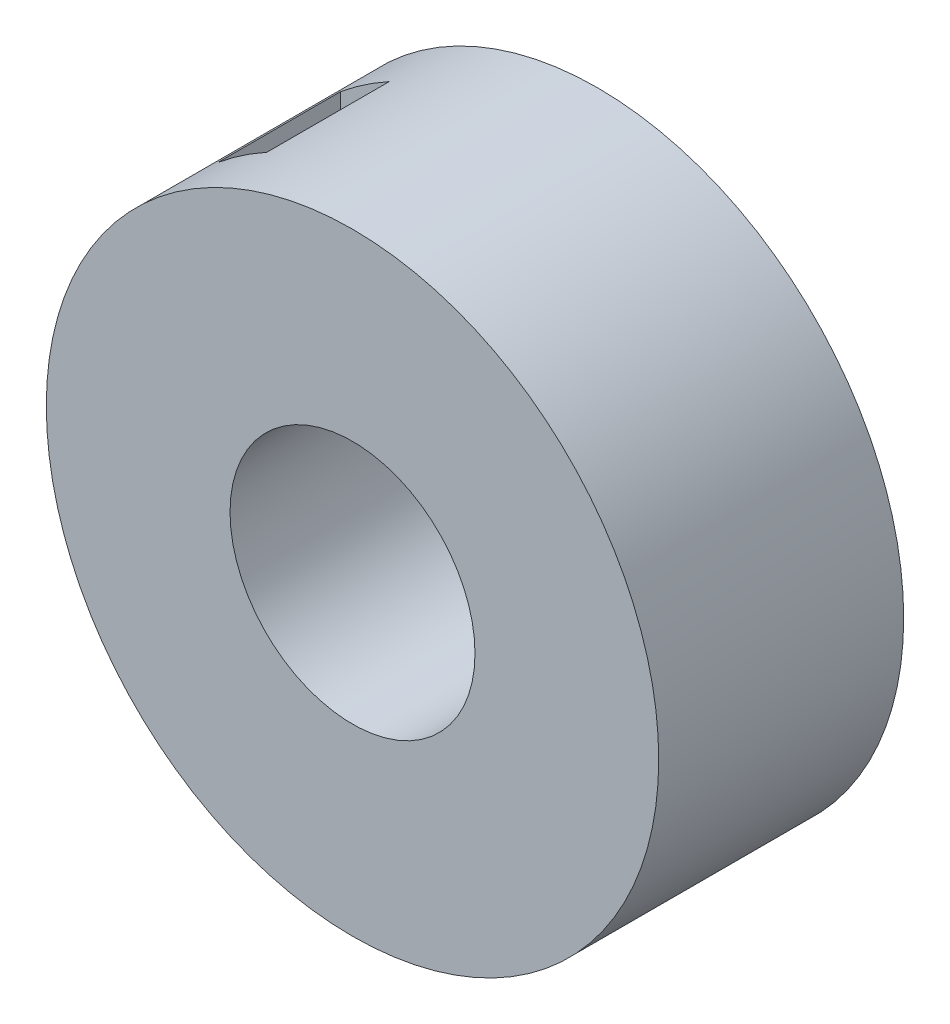
SolidWorks part; units mm, degrees
ref_plane "Alzado" through (0, 0, 0) normal (0, 0, 1) x (1, 0, 0)
ref_plane "Planta" through (0, 0, 0) normal (0, 1, 0) x (1, 0, 0)
ref_plane "Vista lateral" through (0, 0, 0) normal (1, 0, 0) x (0, 0, -1)
sketch "Croquis1" plane through (0, 0, 0) normal (0, 0, 1) x (1, 0, 0)
  circle A0 centre (0, 0) radius 0.625
  circle A1 centre (0, 0) radius 0.25
  dimension "D1" = 1.25
  dimension "D2" = 0.5
extrude "Saliente-Extruir1" add sketch "Croquis1" along normal blind 0.25 and the other way blind 0.25
sketch "Croquis2" plane through (0, 0, 0) normal (0, 0, 1) x (1, 0, 0)
  line L0 (-0.35, -0.5178) -> (-0.35, 0.5178) construction
  line L1 (-0.3, -0.5483) -> (-0.3, 0.5483)
  line L2 (-0.4, -0.4802) -> (-0.4, 0.4802)
  line L4 (-0.3, -0.6096) -> (-0.3, 0.6679) construction
  line L5 (-0.4, -0.6096) -> (-0.4, 0.6679) construction
  line L6 (-0.35, -0.6096) -> (-0.35, 0.6679) construction
  circle A0 centre (0, 0) radius 0.625 construction
  arc A1 (-0.3, 0.5483) -> (-0.4, 0.4802) centre (0, 0) ccw
  arc A2 (-0.4, -0.4802) -> (-0.3, -0.5483) centre (0, 0) ccw
  dimension "D1" = 0.35
  dimension "D2" = 0.05
  dimension "D3" = 0.05
extrude "Cortar-Extruir1" cut sketch "Croquis2" against normal blind 0.125 and the other way blind 0.125
